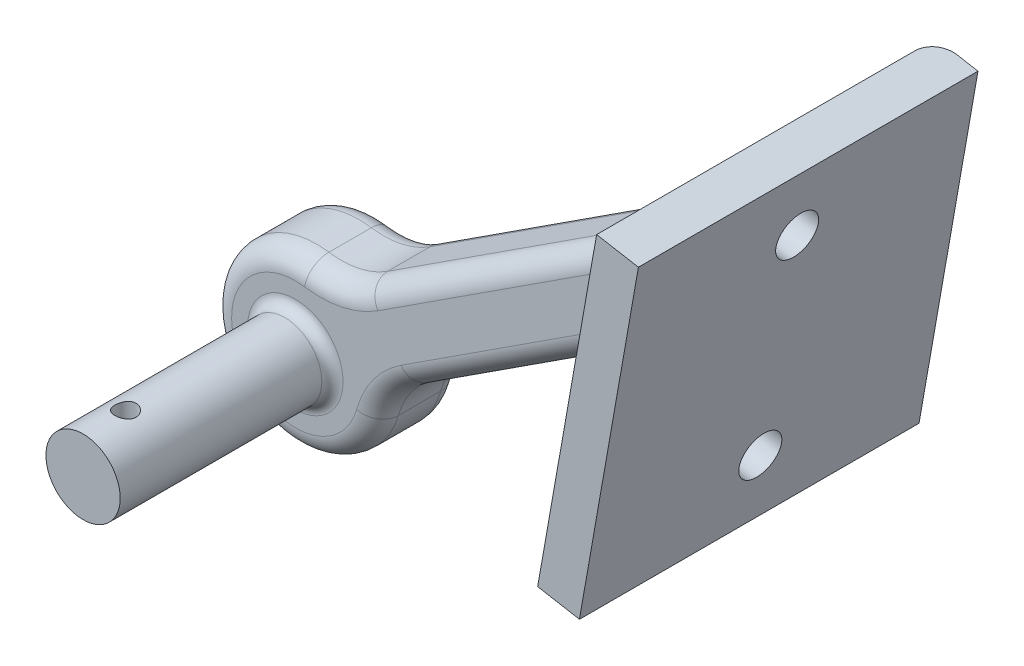
SolidWorks part; units mm, degrees
ref_plane "Front" through (0, 0, 0) normal (0, 0, 1) x (1, 0, 0)
ref_plane "Top" through (0, 0, 0) normal (0, 1, 0) x (1, 0, 0)
ref_plane "Right" through (0, 0, 0) normal (1, 0, 0) x (0, 0, -1)
sketch "Sketch1" plane through (0, 0, 0) normal (0, 0, 1) x (1, 0, 0)
  line L0 (0, 0) -> (25.4, 144.0506) construction
  line L1 (25.4, 144.0506) -> (25.4, 0) construction
  line L2 (25.4, 0) -> (0, 0) construction
  line L3 (4.4107, 25.0141) -> (-1.8429, 26.1168)
  line L4 (-1.8429, 26.1168) -> (6.9785, 76.145)
  line L5 (6.9785, 76.145) -> (13.232, 75.0424)
  line L6 (13.232, 75.0424) -> (4.4107, 25.0141)
  line L7 (-76.2, 0) -> (2.5678, 51.1309) construction
  circle A0 centre (-76.2, 0) radius 12.7
  dimension "D1" = 25.4
  dimension "D2" = 76.2
  dimension "D3" = 50.8
  dimension "D4" = 25.4
  dimension "D5" = 6.35
  dimension "D6" = 10
  dimension "D7" = 25.4
sketch "Sketch2" plane through (0, 0, 0) normal (0, 0, 1) x (1, 0, 0)
  line L0 (-1.8429, 26.1168) -> (6.9785, 76.145) construction
  line L1 (1.0604, 42.5818) -> (4.0752, 59.68)
  line L2 (-56.7711, 12.612) -> (60.7287, 88.8851) construction
  line L3 (-76.2, 0) -> (2.5678, 51.1309) construction
  line L4 (-70.4321, 11.3147) -> (4.0752, 59.68)
  line L5 (-63.5173, 0.6622) -> (1.0604, 42.5818)
  circle A0 centre (-76.2, 0) radius 12.7 construction
  arc A1 (-70.4321, 11.3147) -> (-63.5173, 0.6622) centre (-76.2, 0) ccw
  dimension "D1" = 12.7
extrude "Base-Extrude" add sketch "Sketch2" along normal blind 12.7
sketch "Sketch3" plane through (0, 0, 0) normal (0, 0, 1) x (1, 0, 0)
  line L4 (4.4107, 25.0141) -> (-1.8429, 26.1168)
  line L5 (13.232, 75.0424) -> (4.4107, 25.0141)
  line L6 (6.9785, 76.145) -> (13.232, 75.0424)
  line L7 (-1.8429, 26.1168) -> (6.9785, 76.145)
  line L8 (4.4107, 25.0141) -> (-1.8429, 26.1168)
  line L9 (13.232, 75.0424) -> (4.4107, 25.0141)
  line L10 (6.9785, 76.145) -> (13.232, 75.0424)
  line L11 (-1.8429, 26.1168) -> (6.9785, 76.145)
  dimension "D1" = 0
extrude "Boss-Extrude1" add sketch "Sketch3" along normal blind 50.8
fillet "Fillet1" radius 12.7 2 edges at (-63.5173, 0.6622, 6.35) (-70.4321, 11.3147, 6.35)
sketch "Sketch5" plane through (-6.2535, 1.1027, 0) normal (-0.9848, 0.1736, 0) x (0, 0, 1)
  line L0 (25.4, 76.2) -> (25.4, 25.4) construction
  line L1 (50.8, 76.2) -> (0, 76.2) construction
  line L2 (50.8, 25.4) -> (0, 25.4) construction
  circle A0 centre (25.4, 66.675) radius 3.175
  circle A1 centre (25.4, 34.925) radius 3.175
  dimension "D3" = 6.35
  dimension "D4" = 6.35
  dimension "D1" = 9.525
  dimension "D2" = 9.525
extrude "Cut-Extrude2" cut sketch "Sketch5" against normal through all
fillet "Fillet4" radius 9.525 2 edges at (4.0752, 59.68, 6.35) (1.0604, 42.5818, 6.35)
fillet "Fillet5" radius 3.175 15 edges at (3.3566, 60.1558, 12.7) (-7.6778, 32.3485, 0) (-32.4826, 35.9491, 12.7) (-37.4064, 17.6117, 0) (-69.7784, 12.717, 12.7) (-61.9703, 0.6885, 0) (-86.8524, -6.9149, 12.7) (-86.8524, -6.9149, 0) (5.8865, 69.9524, 0) (-61.9703, 0.6885, 12.7) (-7.6778, 32.3485, 12.7) (-69.7784, 12.717, 0) (3.3566, 60.1558, 0) (-37.4064, 17.6117, 12.7) (-32.4826, 35.9491, 0)
sketch "Sketch6" plane through (0, 0, 12.7) normal (0, 0, 1) x (1, 0, 0)
  circle A0 centre (-76.2, 0) radius 5.5563
  dimension "D1" = 11.1125
extrude "Boss-Extrude2" add sketch "Sketch6" along normal blind 31.75
fillet "Fillet9" radius 1.5875 4 edges at (-1.6488, 27.2176, 11.3088) (3.8228, 58.2485, 12.236) (1.195, 43.3451, 12.7) (-70.6438, 0, 12.7)
sketch "Sketch7" plane through (0, 0, 0) normal (0, 1, 0) x (1, 0, 0)
  line L0 (-76.2, -9.525) -> (-76.2, -3.175) construction
  line L1 (1.5012, -12.7) -> (-63.8369, -12.7) construction
  circle A0 centre (-76.2, -38.1) radius 1.5875
  dimension "D1" = 3.175
  dimension "D2" = 25.4
extrude "Cut-Extrude3" cut sketch "Sketch7" along normal through all and the other way through all
